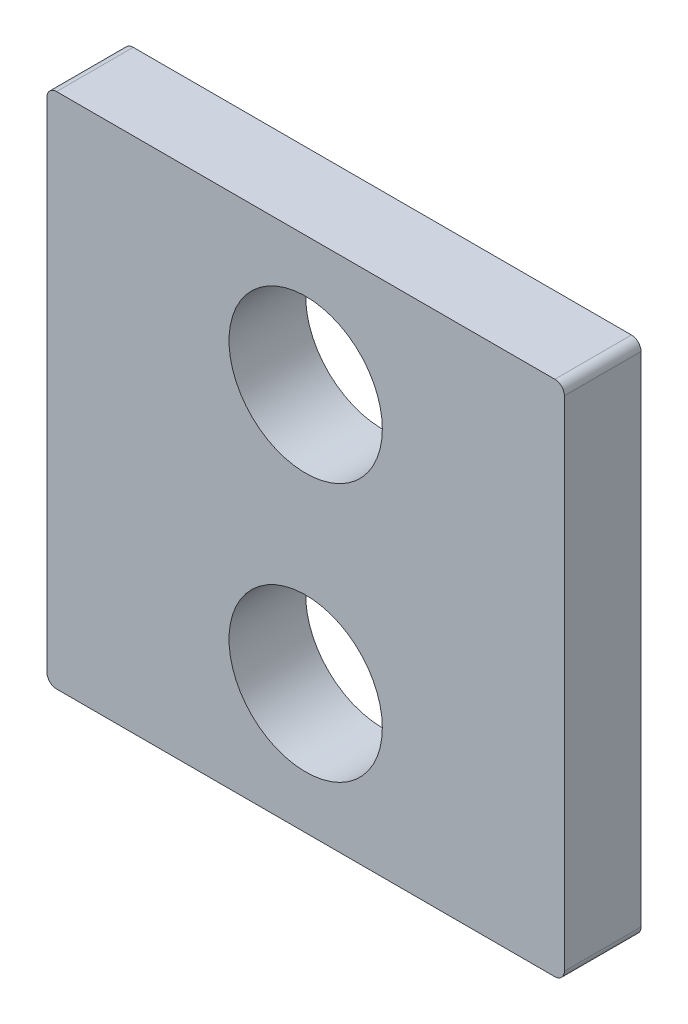
SolidWorks part; units mm, degrees
material "Beech"
ref_plane "Front Plane" through (0, 0, 0) normal (0, 0, 1) x (1, 0, 0)
ref_plane "Top Plane" through (0, 0, 0) normal (0, 1, 0) x (1, 0, 0)
ref_plane "Right Plane" through (0, 0, 0) normal (1, 0, 0) x (0, 0, -1)
sketch "Sketch1" plane through (0, 0, 0) normal (0, 0, 1) x (1, 0, 0)
  line L1 (150.065, 69.0432) -> (150.065, -13.5068)
  line L2 (151.6525, -15.0943) -> (234.2025, -15.0943)
  line L3 (235.79, -13.5068) -> (235.79, 69.0432)
  line L4 (234.2025, 70.6307) -> (151.6525, 70.6307)
  line L5 (148.4775, 69.0432) -> (148.4775, -13.5068)
  line L6 (234.2025, 72.2182) -> (151.6525, 72.2182)
  line L7 (237.3775, -13.5068) -> (237.3775, 69.0432)
  line L8 (151.6525, -16.6818) -> (234.2025, -16.6818)
  line L9 (148.4775, 69.0432) -> (148.4775, -13.5068) construction
  line L10 (234.2025, 72.2182) -> (151.6525, 72.2182) construction
  line L11 (237.3775, -13.5068) -> (237.3775, 69.0432) construction
  line L12 (151.6525, -16.6818) -> (234.2025, -16.6818) construction
  arc A0 (150.065, -13.5068) -> (151.6525, -15.0943) centre (151.6525, -13.5068) ccw
  arc A1 (234.2025, -15.0943) -> (235.79, -13.5068) centre (234.2025, -13.5068) ccw
  arc A2 (235.79, 69.0432) -> (234.2025, 70.6307) centre (234.2025, 69.0432) ccw
  arc A3 (151.6525, 70.6307) -> (150.065, 69.0432) centre (151.6525, 69.0432) ccw
  arc A4 (151.6525, 72.2182) -> (148.4775, 69.0432) centre (151.6525, 69.0432) ccw
  arc A5 (237.3775, 69.0432) -> (234.2025, 72.2182) centre (234.2025, 69.0432) ccw
  arc A6 (234.2025, -16.6818) -> (237.3775, -13.5068) centre (234.2025, -13.5068) ccw
  arc A7 (148.4775, -13.5068) -> (151.6525, -16.6818) centre (151.6525, -13.5068) ccw
  arc A8 (151.6525, 72.2182) -> (148.4775, 69.0432) centre (151.6525, 69.0432) ccw construction
  arc A9 (237.3775, 69.0432) -> (234.2025, 72.2182) centre (234.2025, 69.0432) ccw construction
  arc A10 (234.2025, -16.6818) -> (237.3775, -13.5068) centre (234.2025, -13.5068) ccw construction
  arc A11 (148.4775, -13.5068) -> (151.6525, -16.6818) centre (151.6525, -13.5068) ccw construction
  dimension "D1" = 0
  dimension "D2" = 1.5875
extrude "Boss-Extrude1" add sketch "Sketch1" against normal blind 12.7
hole_wizard "1 (1) Diameter Hole1" positions "Sketch3" profile "Sketch4" hole size "1" standard "ANSI Inch" end condition up to next
sketch "Sketch3" plane through (0, 0, 0) normal (0, 0, 1) x (1, 0, 0)
  line L0 (192.9275, 70.6307) -> (192.9275, 27.7682) construction
  line L1 (234.2025, 70.6307) -> (151.6525, 70.6307) construction
  line L2 (192.9275, 27.7682) -> (192.9275, -15.0943) construction
  line L3 (151.6525, -15.0943) -> (234.2025, -15.0943) construction
  point P11 (192.9275, 49.1995)
  point P13 (192.9275, 6.337)
sketch "Sketch4" plane through (192.9275, 6.337, 0) normal (1, 0, 0) x (0, -1, 0)
  line L0 (0, 0) -> (0, 12.7)
  line L1 (0, 12.7) -> (12.7, 12.7)
  line L2 (12.7, 12.7) -> (12.7, 0)
  line L5 (12.7, 0) -> (0, 0)
  line L11 (0, -6.35) -> (0, 107.95) construction
  dimension "Thru Hole Dia." = 25.4
  dimension "Thru Hole Depth" = 12.7
